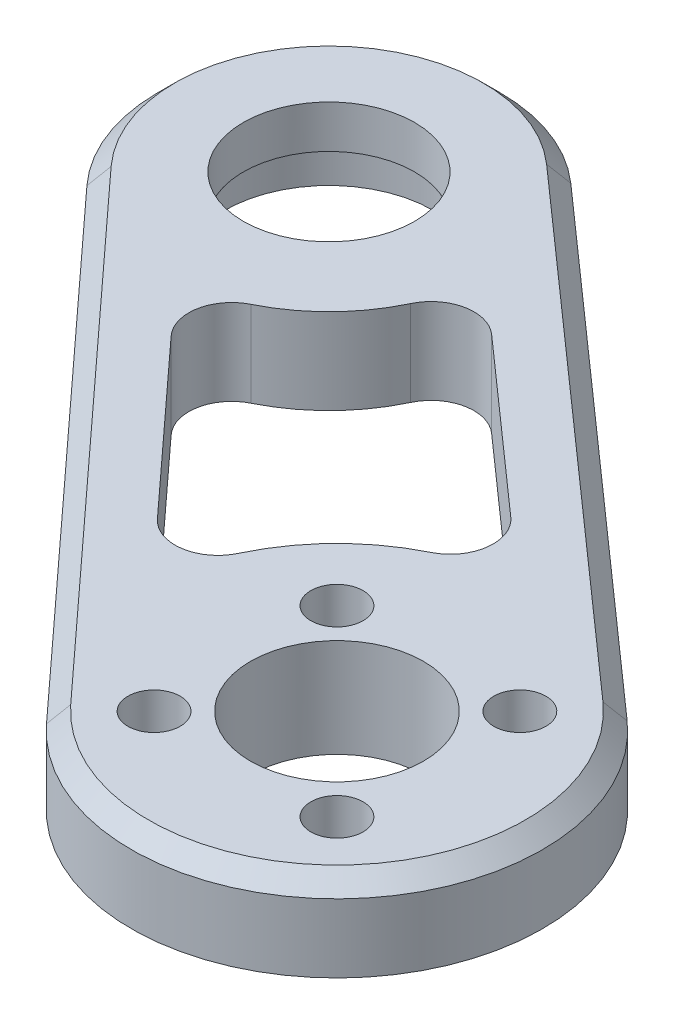
SolidWorks part; units mm, degrees
material "PLA Infill"
ref_plane "Front Plane" through (0, 0, 0) normal (0, 0, 1) x (1, 0, 0)
ref_plane "Top Plane" through (0, 0, 0) normal (0, 1, 0) x (1, 0, 0)
ref_plane "Right Plane" through (0, 0, 0) normal (1, 0, 0) x (0, 0, -1)
sketch "Sketch1" plane through (0, 0, 0) normal (0, 1, 0) x (1, 0, 0)
  line L0 (0, 0) -> (55, 54.0672) construction
  line L1 (55, 54.0672) -> (-55, 54.0672) construction
  line L2 (-55, 54.0672) -> (0, 0) construction
  line L3 (-69.7415, 40.551) -> (-17.6898, -16.2194)
  line L4 (-41.7379, 69.0378) -> (15.9145, 17.9646)
  line L5 (-47.6255, 28.2677) -> (-29.9271, 8.9649)
  line L6 (-29.0781, 47.135) -> (-9.4754, 29.7694)
  circle A0 centre (0, 0) radius 10.1
  circle A1 centre (-55, 54.0672) radius 10
  circle A2 centre (0, 0) radius 24 construction
  circle A3 centre (-55, 54.0672) radius 20 construction
  arc A4 (-69.7415, 40.551) -> (-41.7379, 69.0378) centre (-55, 54.0672) cw
  arc A5 (-17.6898, -16.2194) -> (15.9145, 17.9646) centre (0, 0) ccw
  arc A6 (-46.1521, 36.1308) -> (-36.9149, 45.5274) centre (-55, 54.0672) ccw
  arc A7 (-21.7173, 10.2157) -> (-10.5856, 21.5394) centre (0, 0) cw
  arc A8 (-29.9271, 8.9649) -> (-21.7173, 10.2157) centre (-26.2417, 12.3439) ccw
  arc A9 (-9.4754, 29.7694) -> (-10.5856, 21.5394) centre (-12.7909, 26.0268) cw
  arc A10 (-29.0781, 47.135) -> (-36.9149, 45.5274) centre (-32.3936, 43.3924) ccw
  arc A11 (-47.6255, 28.2677) -> (-46.1521, 36.1308) centre (-43.9401, 31.6467) cw
  point P22 (-23.8825, 2.3723)
  point P25 (-2.7804, 23.8384)
  point P28 (-35.0663, 52.4399)
  point P31 (-53.032, 34.1643)
  dimension "D3" = 20.2
  dimension "D4" = 20
  dimension "D5" = 48
  dimension "D6" = 40
  dimension "D9" = 5
  dimension "D1" = 77.125
  dimension "D2" = 110
  dimension "D7" = 8
  dimension "D8" = 8
extrude "Main Body" add sketch "Sketch1" along normal blind 10
sketch "Sketch2" plane through (0, 0, 0) normal (0, -1, 0) x (1, 0, 0)
  circle A0 centre (-55, -54.0672) radius 10 construction
  circle A1 centre (-55, -54.0672) radius 10 construction
  circle A2 centre (-55, -54.0672) radius 12.2
  dimension "D1" = 24.4
extrude "Bearing Recess" cut sketch "Sketch2" against normal blind 5
sketch "Sketch3" plane through (0, 0, 0) normal (0, -1, 0) x (1, 0, 0)
  circle A0 centre (0, 0) radius 21.5
  circle A1 centre (0, 0) radius 10.1
  circle A2 centre (0, 0) radius 10.1 construction
  dimension "D1" = 43
extrude "Standoff Section" add sketch "Sketch3" along normal blind 1.5
sketch "Sketch4" plane through (0, -1.5, 0) normal (0, -1, 0) x (1, 0, 0)
  line L0 (0, 0) -> (50000, 0) construction
  line L1 (55, -54.0672) -> (-55, -54.0672) construction
  line L2 (-10.6773, 10.6773) -> (0, 0) construction
  circle A0 centre (-10.6773, 10.6773) radius 3.05
  circle A2 centre (10.6773, 10.6773) radius 3.05
  circle A3 centre (10.6773, -10.6773) radius 3.05
  circle A4 centre (-10.6773, -10.6773) radius 3.05
  dimension "D1" = 6.1
  dimension "D2" = 15.1
  dimension "D3" = 45
  dimension "D4" = 4
extrude "M6 Bolt holes" cut sketch "Sketch4" against normal through all
chamfer "Chamfer1" distance 2 angle 45 4 edges at (17.1151, 10, 16.8248) (-12.9117, 10, -43.5012) (-43.7157, 10, -12.1658) (-69.2626, 10, -68.0879)
